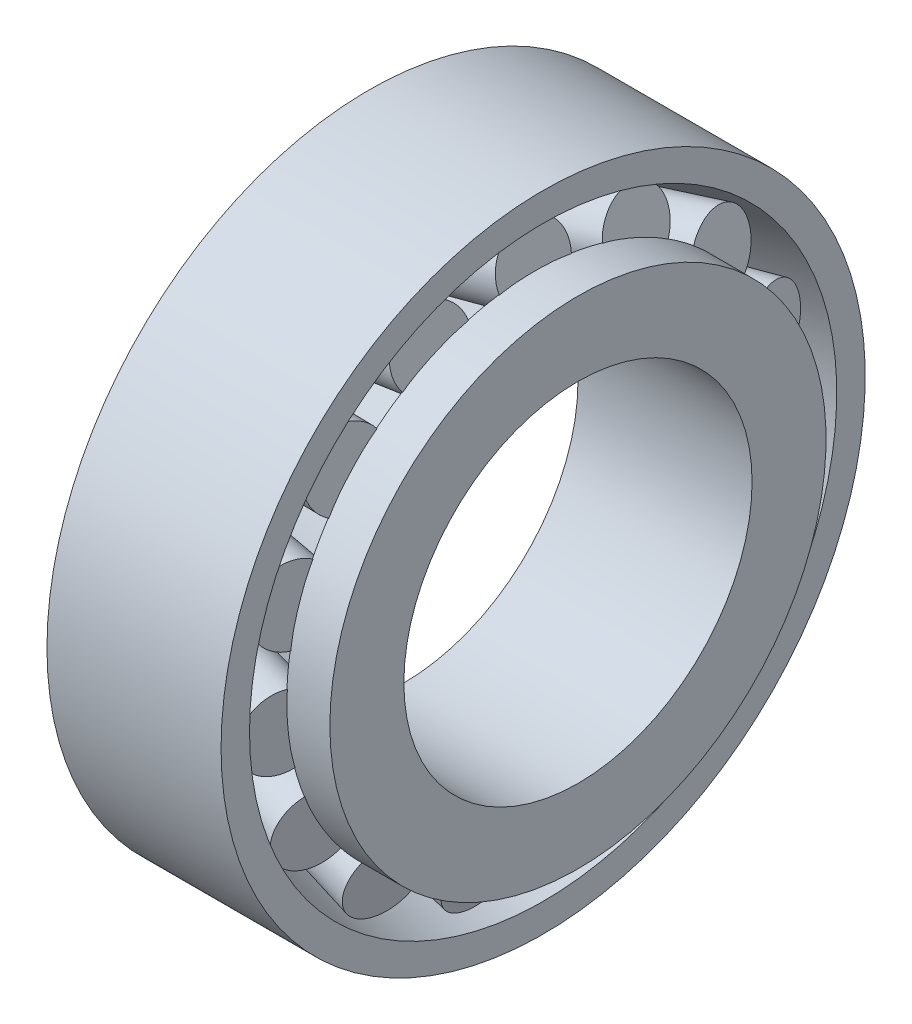
SolidWorks part; units mm, degrees
ref_plane "前视基准面" through (0, 0, 0) normal (0, 0, 1) x (1, 0, 0)
ref_plane "上视基准面" through (0, 0, 0) normal (0, 1, 0) x (1, 0, 0)
ref_plane "右视基准面" through (0, 0, 0) normal (1, 0, 0) x (0, 0, -1)
other "Configuration Table"
sketch "草图3" plane through (0, 0, 0) normal (0, 0, 1) x (1, 0, 0)
  line L0 (0, 0) -> (64.9069, 0) construction
  line L1 (0, 0) -> (0, 18.5) construction
  line L2 (0, 18.5) -> (10, 18.5)
  line L3 (10, 18.5) -> (10, 16.8656)
  line L4 (0, 18.5) -> (0, 14.1862)
  line L5 (0, 14.1862) -> (10, 16.8656)
  line L6 (2, 10) -> (12, 10)
  line L7 (12, 10) -> (12, 14.25)
  line L8 (12, 14.25) -> (9.5219, 14.25)
  line L10 (2, 12.13) -> (2, 10)
  line L11 (9.5219, 14.25) -> (10, 12.4657)
  line L12 (10, 12.4657) -> (3.8515, 10.8182)
  line L13 (3.8515, 10.8182) -> (3.5, 12.13)
  line L14 (3.5, 12.13) -> (2, 12.13)
  point P9 (1, 11.9764)
  point P12 (0, 0)
  dimension "D1" = 37
  dimension "D2" = 20
  dimension "D3" = 12
  dimension "D4" = 15
  dimension "D5" = 10
  dimension "D6" = 10
  dimension "D7" = 1.6344
  dimension "D8" = 4.25
  dimension "D9" = 1.5
  dimension "D10" = 4.25
  dimension "D11" = 2.13
revolve "旋转1" add sketch "草图3" angle 360 about L0
sketch "草图4" plane through (0, 0, 0) normal (0, 0, 1) x (1, 0, 0)
  line L0 (3.8586, 10.8305) -> (3.3112, 12.8734)
  line L1 (10, 16.8656) -> (0, 14.1862) construction
  line L4 (9.9878, 12.4728) -> (3.8586, 10.8305)
  line L5 (9.9878, 12.4728) -> (9.4404, 14.5157)
  line L6 (9.4404, 14.5157) -> (3.3112, 12.8734)
  line L7 (3.3112, 12.8734) -> (2.7612, 14.926) construction
  line L8 (10, 12.4657) -> (9.5219, 14.25) construction
  line L10 (3.8515, 10.8182) -> (3.5, 12.13) construction
  line L11 (10, 12.4657) -> (3.8515, 10.8182) construction
  dimension "D1" = 2.115
  dimension "D2" = 0.01
  dimension "D3" = 0.01
  dimension "D4" = 0.01
revolve "旋转3" add sketch "草图4" angle 360 about L6
pattern_circular "阵列(圆周)1" count 15 over 360 about axis through (0, 0, 0) along (-1, 0, 0) of "旋转3" reverse direction yes
